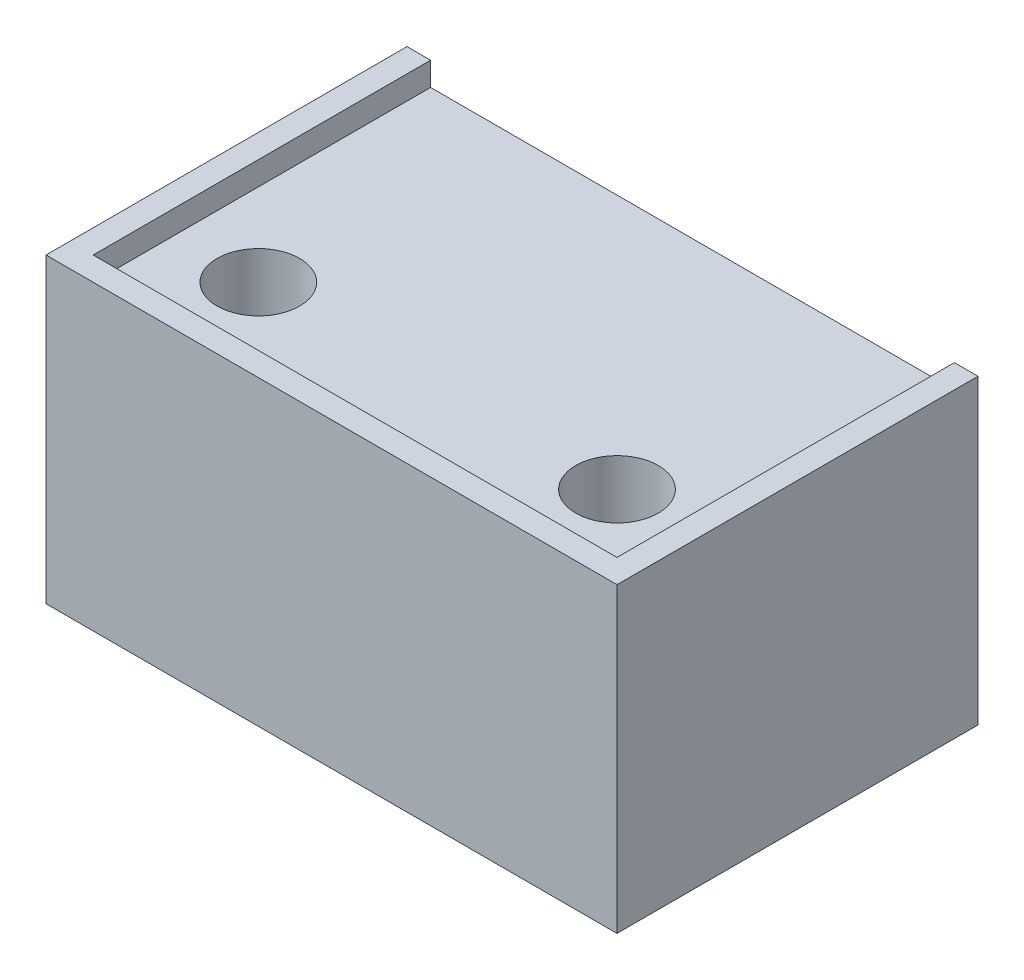
SolidWorks part; units mm, degrees
ref_plane "Front Plane" through (0, 0, 0) normal (0, 0, 1) x (1, 0, 0)
ref_plane "Top Plane" through (0, 0, 0) normal (0, 1, 0) x (1, 0, 0)
ref_plane "Right Plane" through (0, 0, 0) normal (1, 0, 0) x (0, 0, -1)
sketch "Sketch1" plane through (0, 0, 0) normal (0, 1, 0) x (1, 0, 0)
  line L0 (-10.1, 6.65) -> (-11.1, 6.65)
  line L1 (-10.1, -6.65) -> (10.1, -6.65)
  line L2 (-10.1, -6.65) -> (-10.1, 6.65)
  line L3 (-10.1, 6.65) -> (10.1, 6.65)
  line L4 (10.1, -6.65) -> (10.1, 6.65)
  line L5 (-10.1, -6.65) -> (10.1, 6.65) construction
  line L6 (-10.1, 6.65) -> (10.1, -6.65) construction
  line L7 (0, 6.65) -> (0, -6.65) construction
  line L8 (-11.1, 6.65) -> (-11.1, -7.65)
  line L9 (-11.1, -7.65) -> (11.1, -7.65)
  line L10 (11.1, -7.65) -> (11.1, 6.65)
  line L11 (11.1, 6.65) -> (10.1, 6.65)
  line L12 (-11.1, 6.65) -> (-12.1, 6.65)
  line L13 (-12.1, 6.65) -> (-12.1, -8.65)
  line L14 (-12.1, -8.65) -> (12.1, -8.65)
  line L15 (12.1, -8.65) -> (12.1, 6.65)
  line L16 (12.1, 6.65) -> (11.1, 6.65)
  circle A0 centre (-7.6, -4.15) radius 1.75
  circle A1 centre (7.6, -4.15) radius 1.75
  point P0 (0, 0)
  dimension "D3" = 3.5
  dimension "D1" = 13.3
  dimension "D2" = 20.2
  dimension "D4" = 2.5
  dimension "D5" = 2.5
  dimension "D6" = 1
  dimension "D7" = 1
  dimension "D8" = 1
  dimension "D9" = 1
  dimension "D10" = 1
  dimension "D11" = 1
extrude "Boss-Extrude1" add sketch "Sketch1" along normal blind 11.8 contours L1 L4 L3 L2 A0 A1 | L10 L11 L4 L1 L2 L0 L8 L9 region at (-10.3641, 0, 0) region at (0, 0, -0.3202)
extrude "Boss-Extrude2" add sketch "Sketch1<3>" along normal blind 12.8 contours L15 L16 L10 L9 L8 L12 L13 L14 region at (-11.3863, 0, 0.5)
sketch "Sketch1<3>" plane through (0, 0, 0) normal (0, 1, 0) x (1, 0, 0) same geometry as "Sketch1"
